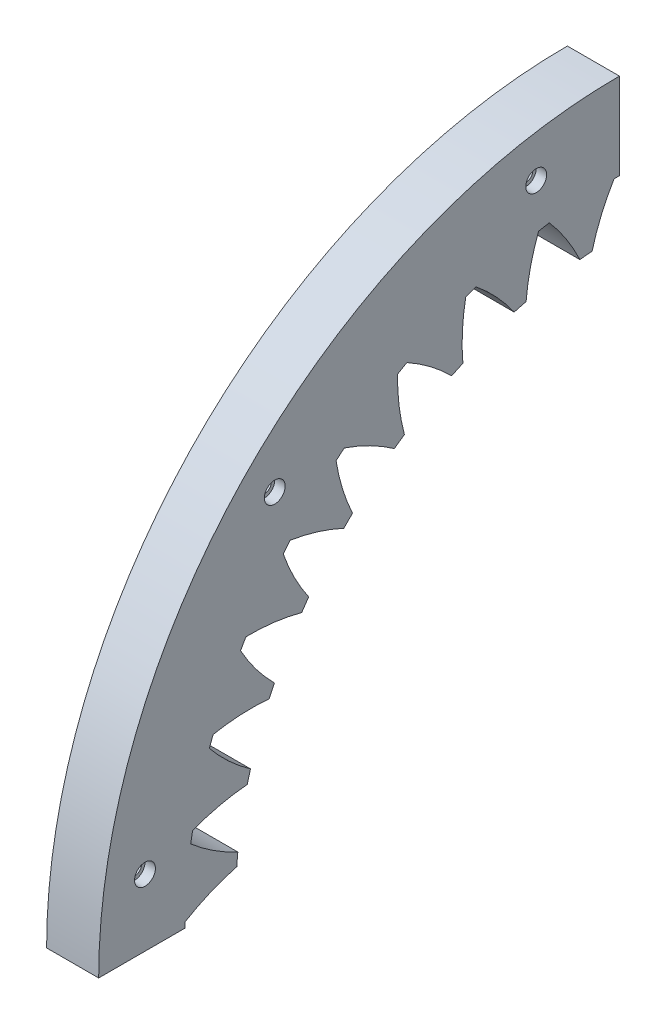
SolidWorks part; units mm, degrees
ref_plane "Plane1" through (0, 0, 0) normal (0, 0, 1) x (1, 0, 0)
ref_plane "Plane2" through (0, 0, 0) normal (0, 1, 0) x (1, 0, 0)
ref_plane "Plane3" through (0, 0, 0) normal (1, 0, 0) x (0, 0, -1)
other "Configuration Table"
sketch "HoldingSke" plane through (0, 0, 0) normal (0, 1, 0) x (1, 0, 0)
  line L0 (0, 0) -> (0.1245, -0.0904)
  line L1 (-15, 0) -> (100, 0) construction
  line L2 (0, 0) -> (-2.1039, 2.3779)
  line L3 (0, 0) -> (-11.863, 4.5341)
  line L4 (0, 0) -> (6.9867, 5.0761)
  line L5 (0, 0) -> (-23.7986, -8.8762)
  line L6 (0, 0) -> (-10.5278, -7.1032)
  line L7 (-2.1039, 2.3779) -> (3.3635, 27.1825)
  line L8 (-76.2, 8.8779) -> (-54.61, 8.8779)
  line L9 (-71.009, 38.7566) -> (-53.1078, 45.2721)
  line L10 (-76.2, 71.12) -> (104.1128, 71.12)
  line L11 (0, 0) -> (-15, 0)
  line L12 (-76.2, 101.6) -> (-75.981, 101.6)
  line L13 (24.9733, 27.94) -> (52.9518, 28.4284)
  line L14 (24.9733, 27.94) -> (24.9743, 27.94)
  line L15 (24.9733, 27.94) -> (100.4006, 29.5858)
  circle A0 centre (0, 0) radius 150
  circle A1 centre (0, 0) radius 12.7
  circle A2 centre (0, 0) radius 12.7
  dimension "Num_teeth" = 36
  dimension "Pitch_radius" = 180.3128
  dimension "Width" = 15
  dimension "Diameter" = 300
sketch "BasProSke" plane through (0, 0, 0) normal (0, 1, 0) x (1, 0, 0)
  line L0 (-10, 0) -> (60, 0) construction
  line L1 (0, 110.5) -> (0, 150)
  line L2 (0, 110.5) -> (15, 110.5)
  line L3 (15, 110.5) -> (15, 150)
  line L4 (15, 150) -> (0, 150)
  dimension "Thickness" = 15
  dimension "Diameter" = 300
revolve "Base-Revolve" add sketch "BasProSke" angle 360 about L0
sketch "TooCutSke" plane through (0, 0, 0) normal (1, 0, 0) x (0, 0, -1)
  line L3 (5.651, 116.8635) -> (5.651, 53.6633) construction
  line L4 (0, 0) -> (0, 59.563) construction
  line L5 (0, 0) -> (-5.9551, 68.0675) construction
  line L6 (-48.6389, 95.0722) -> (29.0748, 101.8713) construction
  circle A0 centre (0, 0) radius 117 construction
  circle A1 centre (0, 0) radius 125.126 construction
  circle A2 centre (0, 0) radius 98.9496 construction
  circle A3 centre (0, 0) radius 110.4746 construction
  arc A4 (7.8729, 110.1937) -> (1.5567, 125.1163) centre (-48.6389, 95.0722) ccw
  arc A5 (7.8729, 110.1937) -> (-7.8729, 110.1937) centre (0, 0) ccw
  arc A6 (1.5567, 125.1163) -> (-1.5567, 125.1163) centre (0, 0) ccw
  arc A7 (-1.5567, 125.1163) -> (-7.8729, 110.1937) centre (48.6389, 95.0722) ccw
extrude "ToothCut" cut sketch "TooCutSke" along normal through all
fillet "Breaks" [suppressed] radius 0.65
fillet "RootFillets" [suppressed] radius 1.626
pattern_circular "TeethCuts" count 36 every 10 about axis through (-10, 0, 0) along (1, 0, 0) of "RootFillets", "Breaks", "ToothCut"
sketch "Croquis1" plane through (15, 0, 0) normal (1, 0, 0) x (0, 0, -1)
  line L1 (0, 0) -> (-205.3766, 0)
  line L2 (0, 0) -> (0, 174.68)
  line L3 (0, 174.68) -> (-205.3766, 174.68)
  line L4 (-205.3766, 0) -> (-205.3766, 174.68)
extrude "Cortar-Extruir1" cut sketch "Croquis1" against normal through all flip side to cut
sketch "Croquis2" plane through (15, 0, 0) normal (1, 0, 0) x (0, 0, -1)
  line L1 (-23.9634, 135.9035) -> (0, 0) construction
  line L2 (0, 0) -> (0, 150) construction
  line L3 (0, 0) -> (-23.9634, 135.9035) construction
  line L4 (0, 0) -> (-64.7871, 121.8468) construction
  line L5 (0, 0) -> (-23.9634, 135.9035) construction
  line L6 (0, 0) -> (-64.7871, 121.8468) construction
  circle A0 centre (0, 0) radius 138 construction
  arc A1 (0, 150) -> (-150, 0) centre (0, 0) ccw construction
  circle A2 centre (-23.9634, 135.9035) radius 2
  circle A3 centre (-64.7871, 121.8468) radius 2
  circle A4 centre (-99.2689, 95.8629) radius 2
  circle A5 centre (-124.0336, 60.4952) radius 2
  circle A6 centre (-136.657, 19.2059) radius 2
  circle A7 centre (-23.9634, 135.9035) radius 3
  circle A8 centre (-64.7871, 121.8468) radius 3
  circle A9 centre (-99.2689, 95.8629) radius 3
  circle A10 centre (-124.0336, 60.4952) radius 3
  circle A11 centre (-136.657, 19.2059) radius 3
  dimension "D1" = 12
  dimension "D2" = 4
  dimension "D6" = 6
  dimension "D3" = 10
  dimension "D5" = 18
  dimension "D8" = 18
  dimension "D4" = 5
  dimension "D7" = 5
extrude "Cortar-Extruir2" cut sketch "Croquis2" against normal through all contours A6 | A4 | A2 region at (15, 135.9035, 23.9634) region at (15, 95.8629, 99.2689) region at (15, 19.2059, 136.657)
extrude "Cortar-Extruir3" cut sketch "Croquis2<3>" against normal blind 3 contours A11 A6 | A9 A4 | A7 A2 region at (15, 135.9035, 26.8786) region at (15, 95.8629, 102.184) region at (15, 19.2059, 139.5721)
sketch "Croquis2<3>" plane through (15, 0, 0) normal (1, 0, 0) x (0, 0, -1) same geometry as "Croquis2"
equation "' \"Module@HoldingSke\" = 6.35"
equation "' \"Num_teeth@HoldingSke\" = 24"
equation "' \"Ap@HoldingSke\" =  14.5"
equation "' \"Ap@HoldingSke\" = 14.5"
equation "' \"Width@HoldingSke\" = 12"
equation "' \"Diameter@HoldingSke\" = 8 * 25.4"
equation "' \"Show_teeth@HoldingSke\" = 100"
equation "' \"Backlash@HoldingSke\" = 0.009 * 25.4"
equation "' \"Addendum_fac@HoldingSke\" = 1.0"
equation "' \"Dedendum_fac@HoldingSke\" = 1.25"
equation "' \"Dedendum_add@HoldingSke\" = 0.00005 * 25.4"
equation "' \"Clearance_fac@HoldingSke\" = 0.25"
equation "\"Pitch@HoldingSke\" = 1 / \"Module@HoldingSke\" "
equation "\"Overcut_dia@TooCutSke\" = (\"Num_teeth@HoldingSke\" - 2 * \"Addendum_fac@HoldingSke\") / \"Pitch@HoldingSke\" - 0.002 * 25.4"
equation "\"Pitch_dia@TooCutSke\" = \"Num_teeth@HoldingSke\" / \"Pitch@HoldingSke\""
equation "\"Base_dia@TooCutSke\" = \"Num_teeth@HoldingSke\" / \"Pitch@HoldingSke\" * cos((\"Ap@HoldingSke\"  * 3.14159265 / 180)) * 0.90"
equation "\"Root_dia@TooCutSke\" = \"Num_teeth@HoldingSke\"  / \"Pitch@HoldingSke\" + 2 *  \"Dedendum_fac@HoldingSke\"/ \"Pitch@HoldingSke\" + \"Dedendum_add@HoldingSke\" * 2"
equation "\"Half_ang@TooCutSke\" = 180 / \"Num_teeth@HoldingSke\""
equation "\"Half_CT@TooCutSke\" = \"Num_teeth@HoldingSke\" / \"Pitch@HoldingSke\" * sin((3.14159265 / 2 / \"Num_teeth@HoldingSke\")) / 2 + 10 * \"Backlash@HoldingSke\" / 4"
equation "\"Flank_rad@TooCutSke\" = \"Num_teeth@HoldingSke\" / \"Pitch@HoldingSke\" / 4"
equation "\"Radius@RootFillets\"= \"Clearance_fac@HoldingSke\" / \"Pitch@HoldingSke\" + \"Dedendum_add@HoldingSke\""
equation "\"Break_rad@Breaks\" = 0.02 / \"Pitch@HoldingSke\" * 5"
equation "\"Num_teeth@TeethCuts\" = int( \"Show_teeth@HoldingSke\" ) + 1"
equation "\"Num_teeth@TeethCuts\" = ((sgn( \"Num_teeth@TeethCuts\" - \"Num_teeth@HoldingSke\" )-1)*( \"Num_teeth@TeethCuts\" - \"Num_teeth@HoldingSke\" ))/-2+ \"Num_teeth@HoldingSke\""
equation "\"Num_teeth@TeethCuts\" = ((sgn( \"Num_teeth@TeethCuts\" - 2.0)+1)*( \"Num_teeth@TeethCuts\" - 2.0))/2 +2.0"
equation "\"Angle@TeethCuts\" = 360.0 / \"Num_teeth@HoldingSke\""
equation "\"Diameter@BasProSke\" = \"Num_teeth@HoldingSke\"  / \"Pitch@HoldingSke\" + 2 *  \"Dedendum_fac@HoldingSke\"/ \"Pitch@HoldingSke\" + \"Dedendum_add@HoldingSke\" * 2 + 0.002 * 25.4"
equation "\"Diameter@BasProSke\" = ((sgn( \"Diameter@BasProSke\"  - \"Diameter@HoldingSke\" )+1)*( \"Diameter@BasProSke\"  - \"Diameter@HoldingSke\" ))/2 + \"Diameter@HoldingSke\""
equation "\"Inside_diameter@BasProSke\" =  (\"Num_teeth@HoldingSke\" - 2 * \"Addendum_fac@HoldingSke\") / \"Pitch@HoldingSke\" "
equation "\"Thickness@BasProSke\"  = \"Width@HoldingSke\""
